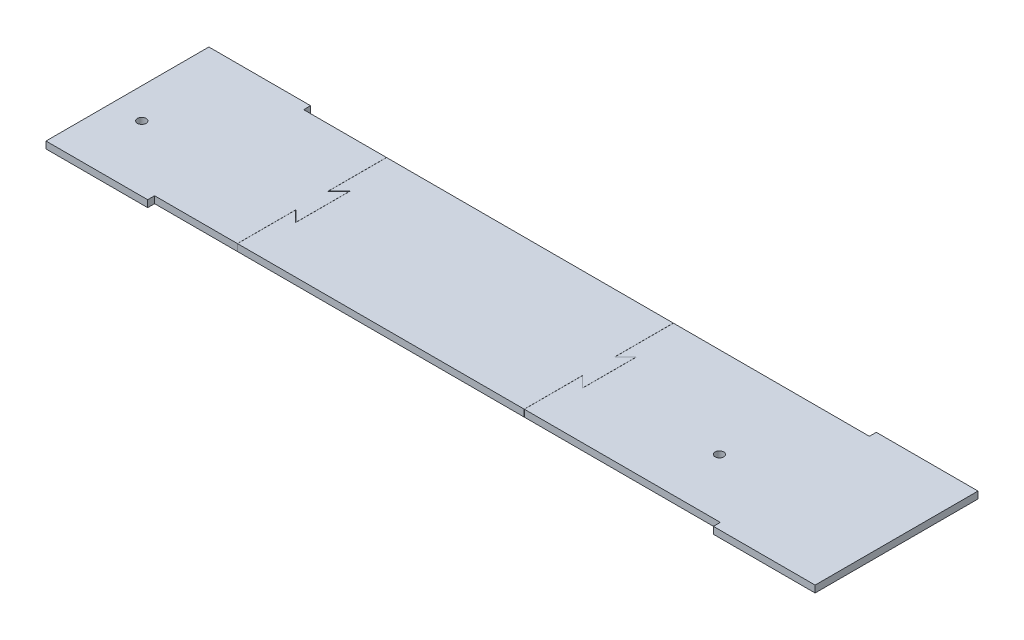
SolidWorks part; units mm, degrees
ref_plane "Front Plane" through (0, 0, 0) normal (0, 0, 1) x (1, 0, 0)
ref_plane "Top Plane" through (0, 0, 0) normal (0, 1, 0) x (1, 0, 0)
ref_plane "Right Plane" through (0, 0, 0) normal (1, 0, 0) x (0, 0, -1)
other "Default"
sketch "Sketch1" plane through (0, 0, 0) normal (0, 1, 0) x (1, 0, 0)
  line L0 (-354.15, 75) -> (-354.15, -75)
  line L1 (-354.15, -75) -> (-260.5, -75)
  line L2 (-260.5, -75) -> (-260.5, -68.65)
  line L3 (-260.5, -68.65) -> (260.5, -68.65)
  line L4 (260.5, -68.65) -> (260.5, -75)
  line L5 (260.5, -75) -> (354.15, -75)
  line L6 (354.15, -75) -> (354.15, 75)
  line L7 (354.15, 75) -> (260.5, 75)
  line L8 (260.5, 75) -> (260.5, 68.65)
  line L9 (260.5, 68.65) -> (-260.5, 68.65)
  line L10 (-260.5, 68.65) -> (-260.5, 75)
  line L11 (-260.5, 75) -> (-354.15, 75)
  point P11 (0, -68.65)
  point P13 (354.15, 0)
  dimension "D1" = 150
  dimension "D2" = 6.35
  dimension "TabWidth" = 93.65
  dimension "Width" = 708.3
extrude "Boss-Extrude1" add sketch "Sketch1" along normal mid plane 6.35
sketch "Sketch2" [suppressed] plane through (0, 3.175, 0) normal (0, 1, 0) x (1, 0, 0)
  line L0 (233.15, -86.7757) -> (233.15, 92.4765) construction
  line L5 (239.5, 75) -> (139.5, 75) construction
  line L6 (43.15, -11.35) -> (183.15, -11.35)
  line L7 (188.15, 88.359) -> (188.15, -110.3451) construction
  line L8 (-49.46, 51.57) -> (-49.46, 61.57) construction
  line L13 (239.5, -75) -> (239.5, 75) construction
  line L14 (38.15, -90.5492) -> (38.15, 114.8099) construction
  line L23 (139.5, 68.65) -> (-139.5, 68.65) construction
  line L24 (-80.91, -8.28) -> (18.15, -8.28) construction
  line L25 (-80.91, -8.28) -> (-80.91, 66.65) construction
  line L26 (-80.91, 66.65) -> (18.15, 66.65) construction
  line L27 (18.15, -8.28) -> (18.15, 66.65) construction
  line L28 (-80.91, -8.28) -> (18.15, 66.65) construction
  line L29 (-80.91, 66.65) -> (18.15, -8.28) construction
  line L30 (-75.83, -3.2) -> (13.07, -3.2) construction
  line L31 (-75.83, -3.2) -> (-75.83, 61.57) construction
  line L32 (-75.83, 61.57) -> (13.07, 61.57) construction
  line L33 (13.07, -3.2) -> (13.07, 61.57) construction
  line L34 (-75.83, -3.2) -> (13.07, 61.57) construction
  line L35 (-75.83, 61.57) -> (13.07, -3.2) construction
  line L36 (-155.36, 15.85) -> (-110.91, 15.85) construction
  line L37 (-155.36, 15.85) -> (-155.36, 66.65) construction
  line L38 (-155.36, 66.65) -> (-110.91, 66.65) construction
  line L39 (-110.91, 15.85) -> (-110.91, 66.65) construction
  line L40 (-155.36, 15.85) -> (-110.91, 66.65) construction
  line L41 (-155.36, 66.65) -> (-110.91, 15.85) construction
  line L42 (-151.55, 19.66) -> (-114.72, 19.66) construction
  line L43 (-151.55, 19.66) -> (-151.55, 62.84) construction
  line L44 (-151.55, 62.84) -> (-114.72, 62.84) construction
  line L45 (-114.72, 19.66) -> (-114.72, 62.84) construction
  line L46 (-151.55, 19.66) -> (-114.72, 62.84) construction
  line L47 (-151.55, 62.84) -> (-114.72, 19.66) construction
  line L48 (-51.46, 51.57) -> (-51.46, 61.57)
  line L49 (-47.46, 51.57) -> (-47.46, 61.57)
  line L50 (-9.46, 51.57) -> (-9.46, 61.57) construction
  line L51 (-11.46, 51.57) -> (-11.46, 61.57)
  line L52 (-7.46, 51.57) -> (-7.46, 61.57)
  line L53 (43.15, -11.35) -> (43.15, 63.65)
  line L54 (43.15, 63.65) -> (183.15, 63.65)
  line L55 (183.15, -11.35) -> (183.15, 63.65)
  line L56 (43.15, -11.35) -> (183.15, 63.65) construction
  line L57 (43.15, 63.65) -> (183.15, -11.35) construction
  line L58 (194.5, 75) -> (188.15, 75)
  line L59 (194.5, 75) -> (194.5, 55)
  line L60 (194.5, 55) -> (188.15, 55)
  line L61 (188.15, 75) -> (188.15, 55)
  line L62 (31.8, -31.35) -> (194.5, -31.35) construction
  line L63 (194.5, -37.7) -> (188.15, -37.7)
  line L64 (194.5, -37.7) -> (194.5, -17.7)
  line L65 (194.5, -17.7) -> (188.15, -17.7)
  line L66 (188.15, -37.7) -> (188.15, -17.7)
  line L67 (38.15, -37.7) -> (31.8, -37.7)
  line L68 (38.15, -37.7) -> (38.15, -17.7)
  line L69 (38.15, -17.7) -> (31.8, -17.7)
  line L70 (31.8, -37.7) -> (31.8, -17.7)
  line L71 (38.15, 55) -> (31.8, 55)
  line L72 (38.15, 55) -> (38.15, 75)
  line L73 (38.15, 75) -> (31.8, 75)
  line L74 (31.8, 55) -> (31.8, 75)
  line L76 (103.15, -31.35) -> (123.15, -31.35)
  line L77 (103.15, -31.35) -> (103.15, -37.7)
  line L78 (103.15, -37.7) -> (123.15, -37.7)
  line L79 (123.15, -31.35) -> (123.15, -37.7)
  circle A0 centre (-75.83, 61.57) radius 1.375
  circle A1 centre (13.07, 61.57) radius 1.375
  circle A2 centre (13.07, -3.2) radius 1.375
  circle A3 centre (-75.83, -3.2) radius 1.375
  circle A4 centre (-42.81, -3.2) radius 1.375
  circle A6 centre (-114.72, 19.66) radius 1.375
  circle A7 centre (-151.55, 19.66) radius 1.375
  circle A8 centre (-151.55, 62.84) radius 1.375
  circle A9 centre (-114.72, 63.48) radius 1.375
  arc A10 (-51.46, 51.57) -> (-47.46, 51.57) centre (-49.46, 51.57) ccw
  arc A11 (-47.46, 61.57) -> (-51.46, 61.57) centre (-49.46, 61.57) ccw
  arc A12 (-11.46, 51.57) -> (-7.46, 51.57) centre (-9.46, 51.57) ccw
  arc A13 (-7.46, 61.57) -> (-11.46, 61.57) centre (-9.46, 61.57) ccw
  point P0 (113.15, 26.15)
  point P28 (-31.38, 29.185)
  point P33 (-31.38, 29.185)
  point P44 (-133.135, 41.25)
  point P49 (-133.135, 41.25)
  point P60 (-49.46, 56.57)
  point P67 (-9.46, 56.57)
  point P85 (113.15, -31.35)
  dimension "D17" = 2.75
  dimension "D25" = 0.64
  dimension "D27" = 2
  dimension "D4" = 6.35
  dimension "D5" = 5
  dimension "D7" = 5
  dimension "D8" = 75
  dimension "D9" = 150
  dimension "D10" = 6.35
  dimension "D12" = 45
  dimension "D13" = 99.06
  dimension "D14" = 74.93
  dimension "D15" = 88.9
  dimension "D16" = 64.77
  dimension "D18" = 2
  dimension "D19" = 20
  dimension "D20" = 33.02
  dimension "D21" = 50.8
  dimension "D22" = 44.45
  dimension "D23" = 36.83
  dimension "D24" = 43.18
  dimension "D26" = 30
  dimension "D28" = 26.37
  dimension "D29" = 22.53
  dimension "D30" = 10
  dimension "D6" = 5
  dimension "D31" = 100
  dimension "D32" = 20
extrude "Back Only" [suppressed] cut sketch "Sketch2" against normal through all
sketch "Sketch3" [suppressed] plane through (0, 3.175, 0) normal (0, 1, 0) x (1, 0, 0)
  line L0 (-225.15, 9.65) -> (-200.15, 9.65) construction
  line L1 (-230.15, -0.35) -> (-195.15, -0.35) construction
  line L2 (-230.15, -0.35) -> (-230.15, 19.65) construction
  line L3 (-230.15, 19.65) -> (-195.15, 19.65) construction
  line L4 (-195.15, -0.35) -> (-195.15, 19.65) construction
  line L5 (-230.15, -0.35) -> (-195.15, 19.65) construction
  line L6 (-230.15, 19.65) -> (-195.15, -0.35) construction
  line L9 (-233.15, -93.1255) -> (-233.15, 99.5323) construction
  line L10 (-239.5, 75) -> (-239.5, -75) construction
  line L11 (139.5, 68.65) -> (38.15, 68.65) construction
  line L12 (0, -88.5309) -> (0, 117.3513) construction
  circle A1 centre (-200.15, 9.65) radius 2.5
  circle A2 centre (-225.15, 9.65) radius 2.5
  circle A3 centre (200.15, 9.65) radius 2.5
  circle A5 centre (225.15, 9.65) radius 2.5
  point P0 (-212.65, 9.65)
  dimension "D4" = 5
  dimension "D1" = 35
  dimension "D2" = 20
  dimension "D5" = 25
  dimension "D6" = 59
  dimension "D7" = 6.35
  dimension "D8" = 3
extrude "Front and Back" [suppressed] cut sketch "Sketch3" against normal through all
sketch "Sketch4" plane through (0, -3.175, 0) normal (0, -1, 0) x (1, 0, 0)
  line L0 (-329.1, -3.15) -> (-323.1, -3.15) construction
  line L1 (202.9, -3.15) -> (208.9, -3.15) construction
  line L2 (-329.1, -3.15) -> (-323.1, -3.15) construction
  line L3 (202.9, -3.15) -> (208.9, -3.15) construction
  line L4 (-184.15, -68.65) -> (-184.15, -15)
  line L5 (260.5, -68.65) -> (-260.5, -68.65) construction
  line L6 (-184.15, -15) -> (-174.15, -25)
  line L7 (-174.15, -25) -> (-174.15, 25)
  line L8 (-174.15, 25) -> (-184.15, 15)
  line L9 (-184.15, 15) -> (-184.15, 68.65)
  line L10 (-260.5, 68.65) -> (260.5, 68.65) construction
  line L11 (-184.25, -68.65) -> (-184.25, -14.7586)
  line L12 (-184.25, -14.7586) -> (-174.25, -24.7586)
  line L13 (-174.25, -24.7586) -> (-174.25, 24.7586)
  line L14 (-174.25, 24.7586) -> (-184.25, 14.7586)
  line L15 (-184.25, 14.7586) -> (-184.25, 68.65)
  line L16 (-184.25, -68.65) -> (-184.15, -68.65)
  line L17 (-184.25, 68.65) -> (-184.15, 68.65)
  line L18 (80, -68.65) -> (80, -15)
  line L19 (80, -15) -> (90, -25)
  line L20 (90, -25) -> (90, 25)
  line L21 (90, 25) -> (80, 15)
  line L22 (80, 15) -> (80, 68.65)
  line L23 (79.9, -68.65) -> (79.9, -14.7586)
  line L24 (79.9, -14.7586) -> (89.9, -24.7586)
  line L25 (89.9, -24.7586) -> (89.9, 24.7586)
  line L26 (89.9, 24.7586) -> (79.9, 14.7586)
  line L27 (79.9, 14.7586) -> (79.9, 68.65)
  line L28 (79.9, -68.65) -> (80, -68.65)
  line L29 (79.9, 68.65) -> (80, 68.65)
  line L30 (-174.15, 0) -> (-354.15, 0) construction
  line L31 (-354.15, -75) -> (-354.15, 75) construction
  line L32 (-184.25, 0) -> (90, 0) construction
  line L33 (79.9, 0) -> (354.15, 0) construction
  line L34 (354.15, 75) -> (354.15, -75) construction
  circle A0 centre (-326.1, 14.85) radius 4
  circle A1 centre (205.9, 14.85) radius 4
  point P8 (205.9, -3.15)
  point P10 (-326.1, -3.15)
  point P14 (-174.15, 0)
  dimension "D1" = 8
  dimension "D2" = 18
  dimension "D3" = 50
  dimension "D4" = 10
  dimension "D7" = 180
  dimension "D5" = 0.1
  dimension "D6" = 2
extrude "Left and Right" cut sketch "Sketch4" against normal through all
sketch "Sketch5" [suppressed] plane through (0, 3.175, 0) normal (0, 1, 0) x (1, 0, 0)
  line L0 (260.5, 68.65) -> (80, 68.65) construction
  line L1 (-155.15, -23.35) -> (-53.15, -23.35) construction
  line L2 (-155.15, -23.35) -> (-155.15, 58.65) construction
  line L3 (-155.15, 58.65) -> (-53.15, 58.65) construction
  line L4 (-53.15, -23.35) -> (-53.15, 58.65) construction
  line L5 (-155.15, -23.35) -> (-53.15, 58.65) construction
  line L6 (-155.15, 58.65) -> (-53.15, -23.35) construction
  line L7 (-354.15, 75) -> (-354.15, -75) construction
  line L9 (-150.65, -28.85) -> (-57.65, -28.85)
  line L10 (-150.65, -28.85) -> (-150.65, 64.15)
  line L11 (-150.65, 64.15) -> (-57.65, 64.15)
  line L12 (-57.65, -28.85) -> (-57.65, 64.15)
  line L13 (-150.65, -28.85) -> (-57.65, 64.15) construction
  line L14 (-150.65, 64.15) -> (-57.65, -28.85) construction
  circle A0 centre (-155.15, 58.65) radius 2.5
  circle A1 centre (-53.15, 58.65) radius 2.5
  circle A2 centre (-53.15, -23.35) radius 2.5
  circle A3 centre (-155.15, -23.35) radius 2.5
  point P0 (-104.15, 17.65)
  point P13 (-104.15, 17.65)
  dimension "D3" = 5
  dimension "D1" = 102
  dimension "D2" = 82
  dimension "D4" = 10
  dimension "D5" = 250
  dimension "D6" = 93
extrude "Right Only" [suppressed] cut sketch "Sketch5" against normal through all
fillet "Right Only 2" [suppressed] radius 5
